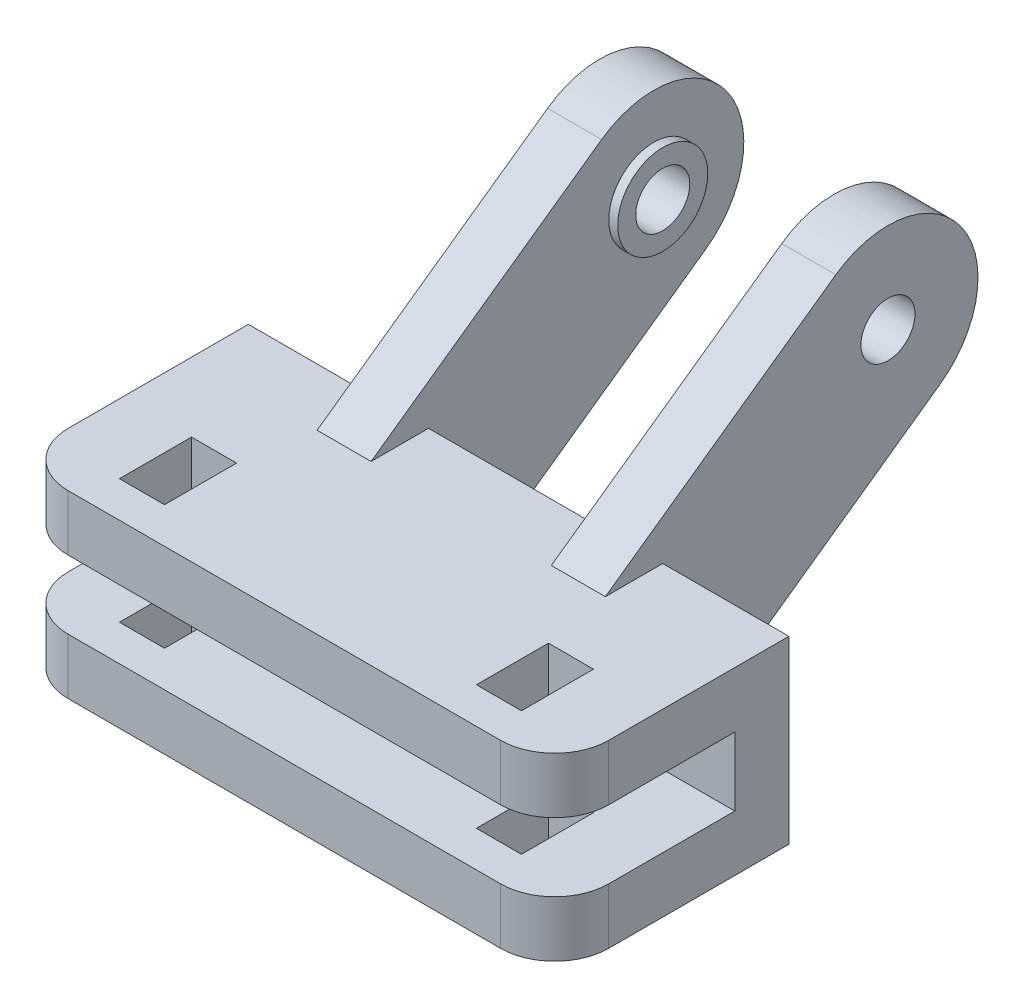
SolidWorks part; units mm, degrees
ref_plane "Plano frontal" through (0, 0, 0) normal (0, 0, 1) x (1, 0, 0)
ref_plane "Plano superior" through (0, 0, 0) normal (0, 1, 0) x (1, 0, 0)
ref_plane "Plano direito" through (0, 0, 0) normal (1, 0, 0) x (0, 0, -1)
sketch "Esboço1" plane through (0, 0, 0) normal (0, 0, 1) x (1, 0, 0)
  line L1 (-15, 5) -> (15, 5)
  line L2 (-15, 5) -> (-15, -5)
  line L3 (-15, -5) -> (15, -5)
  line L4 (15, 5) -> (15, -5)
  line L5 (-15, 5) -> (15, -5) construction
  line L6 (-15, -5) -> (15, 5) construction
  point P0 (0, 0)
  dimension "D1" = 10
  dimension "D2" = 30
extrude "Ressalto-extrusão1" add sketch "Esboço1" along normal blind 13
sketch "Esboço2" plane through (0, 0, 13) normal (0, 0, 1) x (1, 0, 0)
  line L0 (15, -5) -> (15, 5) construction
  line L1 (-15, 1.9) -> (15, 1.9)
  line L2 (-15, 1.9) -> (-15, -1.9)
  line L3 (-15, -1.9) -> (15, -1.9)
  line L4 (15, 1.9) -> (15, -1.9)
  line L5 (-15, 1.9) -> (15, -1.9) construction
  line L6 (-15, -1.9) -> (15, 1.9) construction
  point P0 (0, 0)
  dimension "D1" = 3.8
extrude "Corte-extrusão1" cut sketch "Esboço2" against normal blind 10
fillet "Filete1" radius 3 4 edges at (15, -3.45, 13) (15, 3.45, 13) (-15, 3.45, 13) (-15, -3.45, 13)
sketch "Esboço3" plane through (0, 5, 0) normal (0, 1, 0) x (1, 0, 0)
  line L0 (9.9068, -9) -> (-9.9068, -9) construction
  line L1 (12, -13) -> (-12, -13) construction
  line L2 (11.1568, -11) -> (8.6568, -11)
  line L3 (11.1568, -11) -> (11.1568, -7)
  line L4 (11.1568, -7) -> (8.6568, -7)
  line L5 (8.6568, -11) -> (8.6568, -7)
  line L6 (11.1568, -11) -> (8.6568, -7) construction
  line L7 (11.1568, -7) -> (8.6568, -11) construction
  line L8 (-8.6568, -11) -> (-11.1568, -11)
  line L9 (-8.6568, -11) -> (-8.6568, -7)
  line L10 (-8.6568, -7) -> (-11.1568, -7)
  line L11 (-11.1568, -11) -> (-11.1568, -7)
  line L12 (-8.6568, -11) -> (-11.1568, -7) construction
  line L13 (-8.6568, -7) -> (-11.1568, -11) construction
  point P3 (0, -9)
  dimension "D1" = 2.5
  dimension "D2" = 4
  dimension "D3" = 2
extrude "Corte-extrusão2" cut sketch "Esboço3" against normal through all both and the other way through all
ref_plane "Plano1" through (13, 0, 0) normal (1, 0, 0) x (0, 0, -1)
sketch "Esboço4" plane through (13, 0, 0) normal (1, 0, 0) x (0, 0, -1)
  line L0 (0, 5) -> (0, -5) construction
  line L1 (25, 21) -> (0, 21)
  line L2 (25, 21) -> (25, -4)
  line L3 (25, -4) -> (0, -4)
  line L4 (0, 21) -> (0, -4)
  line L5 (25, 21) -> (0, -4) construction
  line L6 (25, -4) -> (0, 21) construction
  line L7 (-10, -5) -> (0, -5) construction
  point P0 (12.5, 8.5)
  dimension "D1" = 25
  dimension "D2" = 1
extrude "Ressalto-extrusão2" add sketch "Esboço4" against normal mid plane 3
chamfer "Chanfro1" distance 5 angle 60 1 edges at (13, -4, 0) first distance on face at (6.5, 0.25, 0)
chamfer "Chanfro2" distance 7 angle 30 1 edges at (13, 5, 0) first distance on face at (9.9068, 5, 9)
sketch "Esboço5" plane through (11.5, 0, 0) normal (-1, 0, 0) x (0, 0, 1)
  line L0 (-25, 21) -> (0, 21) construction
  line L1 (-4.8, 2.3) -> (-20.2, 2.3) construction
  line L2 (-4.8, 2.3) -> (-4.8, 17.7) construction
  line L3 (-4.8, 17.7) -> (-20.2, 17.7) construction
  line L4 (-20.2, 2.3) -> (-20.2, 17.7) construction
  line L5 (-4.8, 2.3) -> (-20.2, 17.7) construction
  line L6 (-4.8, 17.7) -> (-20.2, 2.3) construction
  circle A0 centre (-12.5, 10) radius 8.5
  circle A1 centre (-20.2, 17.7) radius 1
  circle A2 centre (-4.8, 17.7) radius 1
  circle A3 centre (-4.8, 2.3) radius 1
  circle A4 centre (-20.2, 2.3) radius 1
  point P16 (-12.5, 21)
  dimension "D1" = 17
  dimension "D3" = 2
  dimension "D2" = 15.4
  dimension "D4" = 11
extrude "Corte-extrusão3" cut sketch "Esboço5" against normal blind 3
fillet "Filete2" radius 4 3 edges at (13, -4, -25) (13, 21, -25) (13, 21, 0)
ref_plane "Plano2" through (-5, 0, 0) normal (1, 0, 0) x (0, 0, -1)
sketch "Esboço6" plane through (-5, 0, 0) normal (1, 0, 0) x (0, 0, -1)
  line L0 (9.6066, 14.0778) -> (-3.1873, 5)
  line L3 (15.3934, 5.9222) -> (0, -5)
  line L4 (0, 5) -> (0, -5) construction
  line L5 (-7, 5) -> (0, 5) construction
  line L6 (0, -5) -> (0, 5)
  line L7 (0, 5) -> (-3.1873, 5)
  arc A0 (15.3934, 5.9222) -> (9.6066, 14.0778) centre (12.5, 10) ccw
  circle A1 centre (12.5, 10) radius 1.5
  circle A3 centre (12.5, 10) radius 8.5 construction
  dimension "D1" = 10
  dimension "D2" = 3
extrude "Ressalto-extrusão3" add sketch "Esboço6" against normal blind 3
sketch "Esboço7" plane through (-5, 0, 0) normal (1, 0, 0) x (0, 0, -1)
  circle A0 centre (12.5, 10) radius 1.5
  circle A1 centre (12.5, 10) radius 2.5
  dimension "D1" = 5
extrude "Ressalto-extrusão4" add sketch "Esboço7" along normal blind 0.5
mirror "Espelhar1" about plane through (0, 0, 0) normal (1, 0, 0) of "Ressalto-extrusão4", "Ressalto-extrusão3"
sketch "Esboço8" plane through (15, 0, 0) normal (1, 0, 0) x (0, 0, -1)
  line L0 (0, 5) -> (-7, 5) construction
  line L1 (-7.8941, 22.5219) -> (29.1733, 22.5219)
  line L2 (-7.8941, 22.5219) -> (-7.8941, 5)
  line L3 (-7.8941, 5) -> (0, 5)
  line L4 (29.1733, 22.5219) -> (29.1733, 5)
  line L6 (0, -5) -> (29.1733, -5)
  line L7 (0, -5) -> (0, 5)
  line L9 (29.1733, -5) -> (29.1733, 5)
extrude "Corte-extrusão4" cut sketch "Esboço8" against normal blind 5
